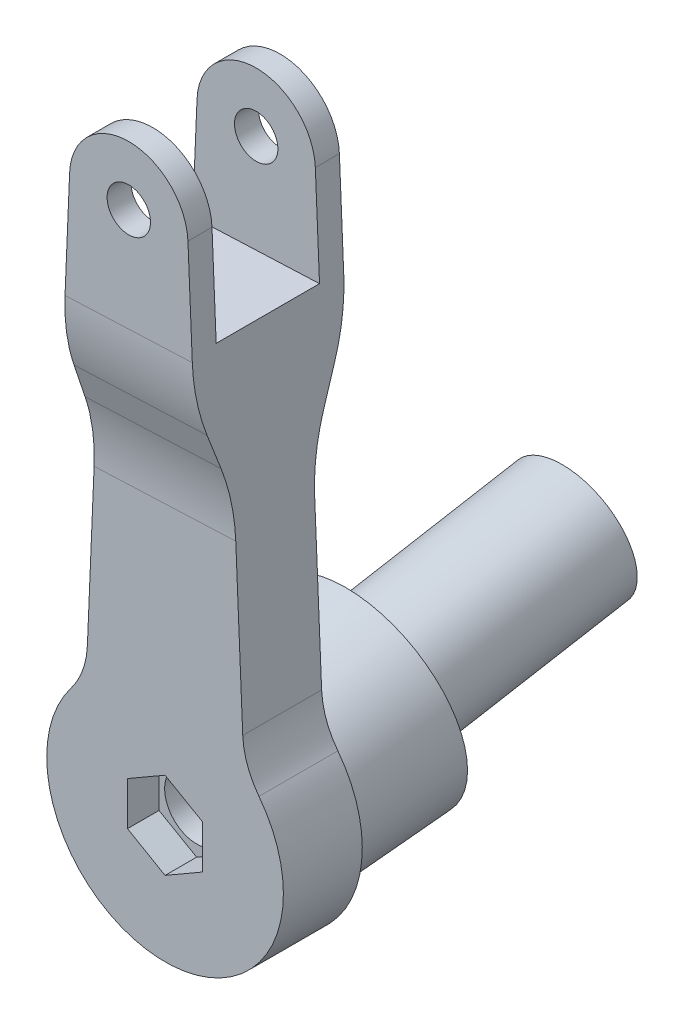
SolidWorks part; units mm, degrees
ref_plane "Front Plane" through (0, 0, 0) normal (0, 0, 1) x (1, 0, 0)
ref_plane "Top Plane" through (0, 0, 0) normal (0, 1, 0) x (1, 0, 0)
ref_plane "Right Plane" through (0, 0, 0) normal (1, 0, 0) x (0, 0, -1)
sketch "Sketch1" plane through (0, 0, 0) normal (0, 0, 1) x (1, 0, 0)
  line L0 (0, 0) -> (0, 69.866) construction
  line L1 (-7.5, 70.1838) -> (-10, 11.1803)
  line L3 (7.5, 70.1838) -> (10, 11.1803)
  arc A6 (-10, 11.1803) -> (10, 11.1803) centre (0, 0) ccw
  circle A7 centre (0, 69.866) radius 2.75
  arc A8 (-7.5, 70.1838) -> (7.5, 70.1838) centre (0, 69.866) cw
  dimension "D1" = 69.866
  dimension "D3" = 30
  dimension "D4" = 5.5
  dimension "D5" = 20
  dimension "D6" = 15
extrude "Boss-Extrude1" add sketch "Sketch1" along normal blind 19.2
sketch "Sketch13" plane through (10.4549, 0.443, 0) normal (0.9991, 0.0423, 0) x (0, 0, -1)
  line L0 (0, 77.3101) -> (-19.2, 77.3101) construction
  line L2 (-16.15, 77.3101) -> (-16.15, 57.3101)
  line L3 (-16.15, 57.3101) -> (-3.05, 57.3101)
  line L4 (-3.05, 77.3101) -> (-3.05, 57.3101)
  line L5 (-16.15, 77.3101) -> (-3.05, 57.3101) construction
  line L6 (-16.15, 57.3101) -> (-3.05, 77.3101) construction
  line L7 (-19.2, 77.3101) -> (-16.15, 77.3101) construction
  line L8 (-19.2, 10.747) -> (-19.2, 69.8034) construction
  line L9 (0, 10.747) -> (0, 69.8034) construction
  line L10 (-19.2, 52.3101) -> (-14.6, 39.6717)
  line L11 (-19.2, 10.747) -> (-19.2, 69.8034) construction
  line L12 (-14.6, 39.6717) -> (-14.6, -15)
  line L13 (-19.2, -15) -> (0, -15) construction
  line L14 (-19.2, 52.3101) -> (-19.2, 77.3101)
  line L15 (-19.2, 77.3101) -> (-16.15, 77.3101)
  line L16 (-9.6, 65.3081) -> (-9.6, -49934.6919) construction
  line L17 (0, 77.3101) -> (-3.05, 77.3101)
  line L18 (0, 52.3101) -> (0, 77.3101)
  line L19 (0, 52.3101) -> (-4.6, 39.6717)
  line L20 (-4.6, 39.6717) -> (-4.6, -15)
  line L21 (-3.05, 77.3101) -> (0, 77.3101) construction
  line L22 (-14.6, -15) -> (-4.6, -15)
  point P4 (-9.6, 67.3101)
  dimension "D1" = 3.05
  dimension "D2" = 20
  dimension "D3" = 160
  dimension "D4" = 5
  dimension "D5" = 10
extrude "Cut-Extrude4" cut sketch "Sketch13" against normal through all both and the other way through all flip side to cut
sketch "Sketch3" plane through (0, 0, 14.6) normal (0, 0, 1) x (1, 0, 0)
  line L1 (0, 5.5) -> (-4.7631, 2.75)
  line L2 (-4.7631, 2.75) -> (-4.7631, -2.75)
  line L3 (-4.7631, -2.75) -> (0, -5.5)
  line L4 (0, -5.5) -> (4.7631, -2.75)
  line L5 (4.7631, -2.75) -> (4.7631, 2.75)
  line L6 (4.7631, 2.75) -> (0, 5.5)
  circle A0 centre (0, 0) radius 4.7631 construction
  dimension "D1" = 9.5263
extrude "Cut-Extrude2" cut sketch "Sketch3" against normal blind 4
sketch "Sketch5" plane through (0, 0, 0) normal (1, 0, 0) x (0, 0, -1)
  line L0 (-5, 0) -> (10.4, 2.7154) construction
  line L1 (0, 52.7062) -> (0, 70.1838) construction
  line L2 (-4.6, 40.0791) -> (-4.6, 11.1803) construction
  line L3 (0, 52.7062) -> (0, 70.1838) construction
  point P13 (10.4, 2.7154)
  dimension "D1" = 10
  dimension "D2" = 5
  dimension "D3" = 15
ref_plane "Plane3" through (0, 2.7154, -10.4) normal (0, 0.1736, -0.9848) x (-1, 0, 0)
sketch "Sketch9" plane through (0, 2.7154, -10.4) normal (0, 0.1736, -0.9848) x (-1, 0, 0)
  circle A0 centre (0, -0.8682) radius 13
  circle A2 centre (0, -0.8682) radius 11 construction
  dimension "D1" = 22
  dimension "D2" = 2
sketch "Sketch4" plane through (0, 0, 10.6) normal (0, 0, 1) x (1, 0, 0)
  circle A0 centre (0, 0) radius 4.05
  dimension "D1" = 8.1
extrude "Cut-Extrude3" cut sketch "Sketch4" against normal blind 20
fillet "Fillet4" radius 10 2 edges at (-10, 11.1803, 9.6) (10, 11.1803, 9.6)
extrude "Boss-Extrude2" add sketch "Sketch9" against normal up to surface (13.0922 mm away) up to face at (0, 4.05, 4.6)
sketch "Sketch10" plane through (0, 1.8604, -10.5508) normal (0, 0.1736, -0.9848) x (-1, 0, 0)
  circle A0 centre (0, 0) radius 8
  dimension "D1" = 16
extrude "Boss-Extrude3" add sketch "Sketch10" along normal blind 27
draft "Draft1" type of draft neutral plane draft angle 3 faces to draft 1 face at (0, 12.3894, 4.6) neutral plane through (0, 1.8604, -10.5508) neutral plane normal (0, 0.1736, -0.9848) reverse direction yes parameters "D1"=3
fillet "Fillet5" radius 25 4 edges at (-0.0148, 52.3564, 0) (-0.0158, 39.7066, 4.6) (-0.0158, 39.7066, 14.6) (-0.0148, 52.3564, 19.2)
sketch "Sketch14" plane through (0, 6.5489, -37.1406) normal (0, 0.1736, -0.9848) x (-1, 0, 0)
  line L0 (0, 0) -> (0, -8) construction
  circle A0 centre (-3.4641, 2) radius 2
  circle A1 centre (3.4641, 2) radius 2
  circle A2 centre (0, -4) radius 2
  circle A4 centre (0, 0) radius 8
  circle A5 centre (0, 0) radius 8 construction
  point P9 (0, 0)
  point P10 (0, -4)
  dimension "D1" = 4
  dimension "D2" = 0
  dimension "D4" = 3
extrude "Cut-Extrude5" cut sketch "Sketch14" against normal blind 4
equation "\"Leg_Tilt\"=10"
equation "\"D1@Sketch5\"=\"Leg_Tilt\""
